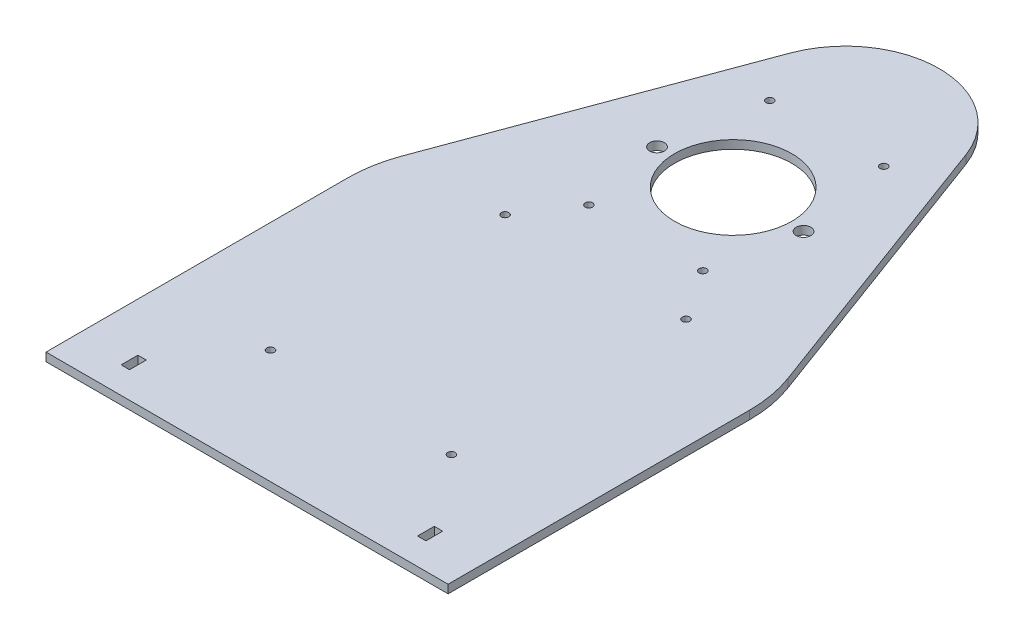
SolidWorks part; units mm, degrees
ref_plane "Front Plane" through (0, 0, 0) normal (0, 0, 1) x (1, 0, 0)
ref_plane "Top Plane" through (0, 0, 0) normal (0, 1, 0) x (1, 0, 0)
ref_plane "Right Plane" through (0, 0, 0) normal (1, 0, 0) x (0, 0, -1)
sketch "Sketch3" plane through (0, 0, 0) normal (0, 1, 0) x (1, 0, 0)
  line L0 (0, 0) -> (0, 114.3)
  line L1 (3.1613, 131.9407) -> (42.8529, 239.1278)
  line L2 (109.5471, 239.1278) -> (149.2387, 131.9407)
  line L3 (152.4, 114.3) -> (152.4, 0)
  line L4 (152.4, 0) -> (0, 0)
  line L5 (76.2, 262.3393) -> (76.2, 0) construction
  line L6 (18.4411, 16.3877) -> (21.6161, 16.3877)
  line L7 (18.4411, 16.3877) -> (18.4411, 10.0377)
  line L8 (18.4411, 10.0377) -> (21.6161, 10.0377)
  line L9 (21.6161, 16.3877) -> (21.6161, 10.0377)
  line L10 (133.9589, 10.0377) -> (130.7839, 10.0377)
  line L11 (130.7839, 16.3877) -> (130.7839, 10.0377)
  line L12 (133.9589, 16.3877) -> (130.7839, 16.3877)
  line L13 (133.9589, 16.3877) -> (133.9589, 10.0377)
  arc A0 (42.8529, 239.1278) -> (109.5471, 239.1278) centre (76.2, 226.7793) cw
  arc A1 (0, 114.3) -> (3.1613, 131.9407) centre (50.8, 114.3) cw
  arc A2 (149.2387, 131.9407) -> (152.4, 114.3) centre (101.6, 114.3) cw
  circle A3 centre (76.2, 184.2441) radius 22.225
  circle A4 centre (103.9598, 183.153) radius 2.7781
  circle A5 centre (48.4402, 183.153) radius 2.7781
  circle A6 centre (41.91, 43.18) radius 1.4224
  circle A7 centre (41.91, 132.08) radius 1.4224
  circle A8 centre (110.49, 132.08) radius 1.4224
  circle A9 centre (110.49, 43.18) radius 1.4224
  circle A10 centre (54.61, 151.1577) radius 1.4224
  circle A11 centre (54.61, 219.7377) radius 1.4224
  circle A12 centre (97.79, 151.1577) radius 1.4224
  circle A13 centre (97.79, 219.7377) radius 1.4224
  dimension "D1" = 35.56
  dimension "D2" = 50.8
  dimension "D3" = 50.8
  dimension "D10" = 43.18
  dimension "D13" = 68.58
  dimension "D4" = 114.3
  dimension "D5" = 152.4
  dimension "D6" = 3.175
  dimension "D7" = 6.35
  dimension "D8" = 18.4411
  dimension "D9" = 107.1871
  dimension "D11" = 88.9
  dimension "D12" = 68.58
  dimension "D14" = 43.18
extrude "Boss-Extrude1" add sketch "Sketch3" along normal blind 3.175
